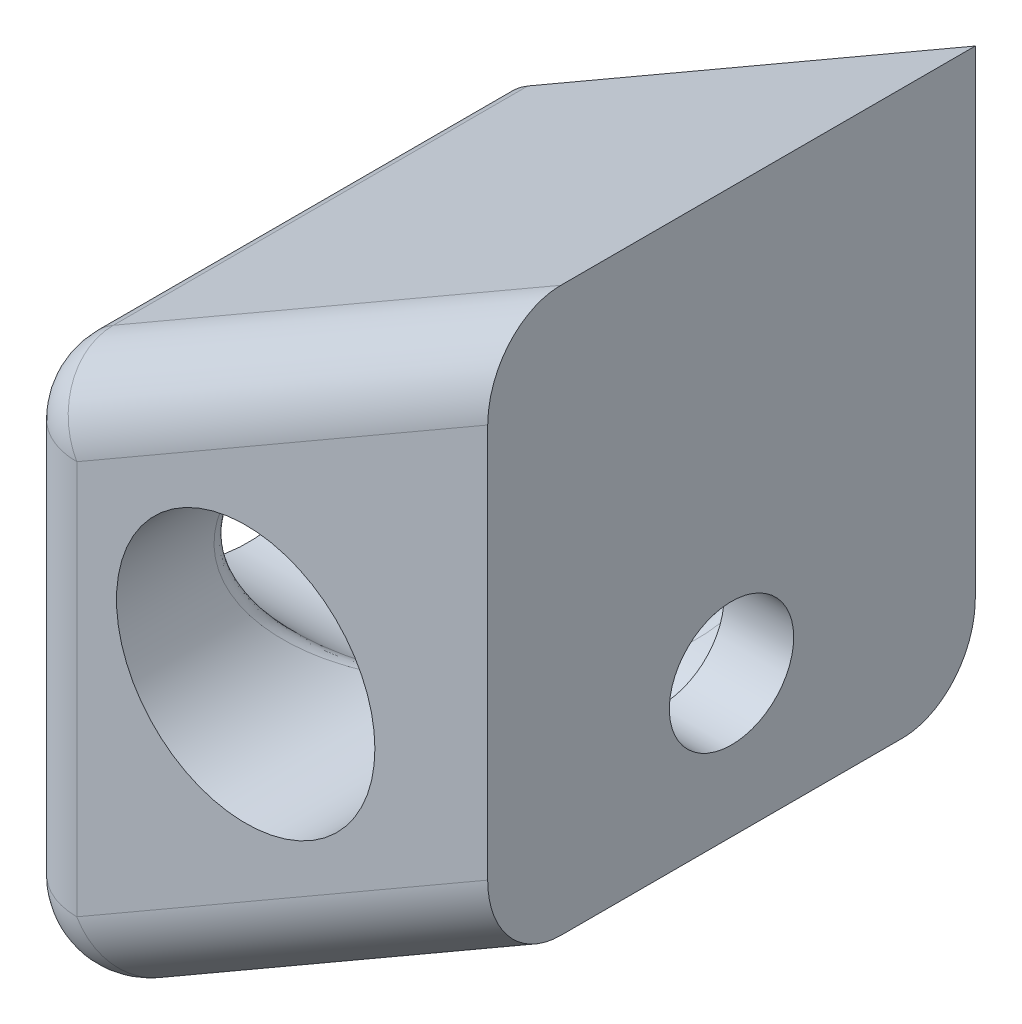
SolidWorks part; units mm, degrees
ref_plane "Front Plane" through (0, 0, 0) normal (0, 0, 1) x (1, 0, 0)
ref_plane "Top Plane" through (0, 0, 0) normal (0, 1, 0) x (1, 0, 0)
ref_plane "Right Plane" through (0, 0, 0) normal (1, 0, 0) x (0, 0, -1)
sketch "Sketch1" plane through (0, 0, 0) normal (0, 0, 1) x (1, 0, 0)
  line L0 (-10, 13.094) -> (9.8544, 24.557)
  line L6 (-10, -10) -> (-10, 13.094)
  line L10 (-10, -10) -> (9.8544, 1.463)
  line L11 (9.8544, 1.463) -> (9.8544, 24.557)
  point P0 (0, 0)
extrude "Boss-Extrude1" add sketch "Sketch1" along normal blind 20
sketch "Sketch4" plane through (0, 0, 0) normal (0, 0, 1) x (1, 0, 0)
  line L0 (-0.0728, 18.8255) -> (-0.0728, -4.2685) construction
  line L1 (9.8544, 24.557) -> (-10, 13.094) construction
  line L2 (-10, -10) -> (9.8544, 1.463) construction
  circle A2 centre (-0.0728, 7.2785) radius 2.55
extrude "Cut-Extrude2" cut sketch "Sketch4" along normal through all
sketch "Sketch5" plane through (0, 0, 0) normal (1, 0, 0) x (0, 0, -1)
  line L0 (-10, 24.557) -> (-10, -10) construction
  line L1 (-20, 24.557) -> (0, 24.557) construction
  circle A0 centre (-10, 7.2785) radius 2.55
extrude "Cut-Extrude3" cut sketch "Sketch5" against normal through all both and the other way through all
sketch "Sketch6" plane through (0, 0, 0) normal (0, 0, 1) x (1, 0, 0)
  circle A1 centre (-0.0728, 7.2785) radius 5.3
extrude "Cut-Extrude4" cut sketch "Sketch6" against normal blind 17 from surface at 20 starting at face at (2.4772, 7.2785, 20)
sketch "Sketch7" plane through (0, 0, 0) normal (1, 0, 0) x (0, 0, -1)
  circle A0 centre (-10, 7.2785) radius 5.3
extrude "Cut-Extrude5" cut sketch "Sketch7" against normal blind 10 and the other way blind 7
fillet "Fillet1" radius 0.7 6 edges at (7, 7.2785, 4.7) (5.2272, 7.2785, 3) (-5.3728, 7.2785, 4.7) (-5.3728, 7.2785, 15.3) (5.2272, 7.2785, 15.3) (5.2272, 7.2785, 4.7)
fillet "Fillet2" radius 3 6 edges at (-0.0728, 18.8255, 20) (-10, 1.547, 20) (-10, 13.094, 10) (-10, -10, 10) (-0.0728, -4.2685, 20) (-0.0728, -4.2685, 0)
